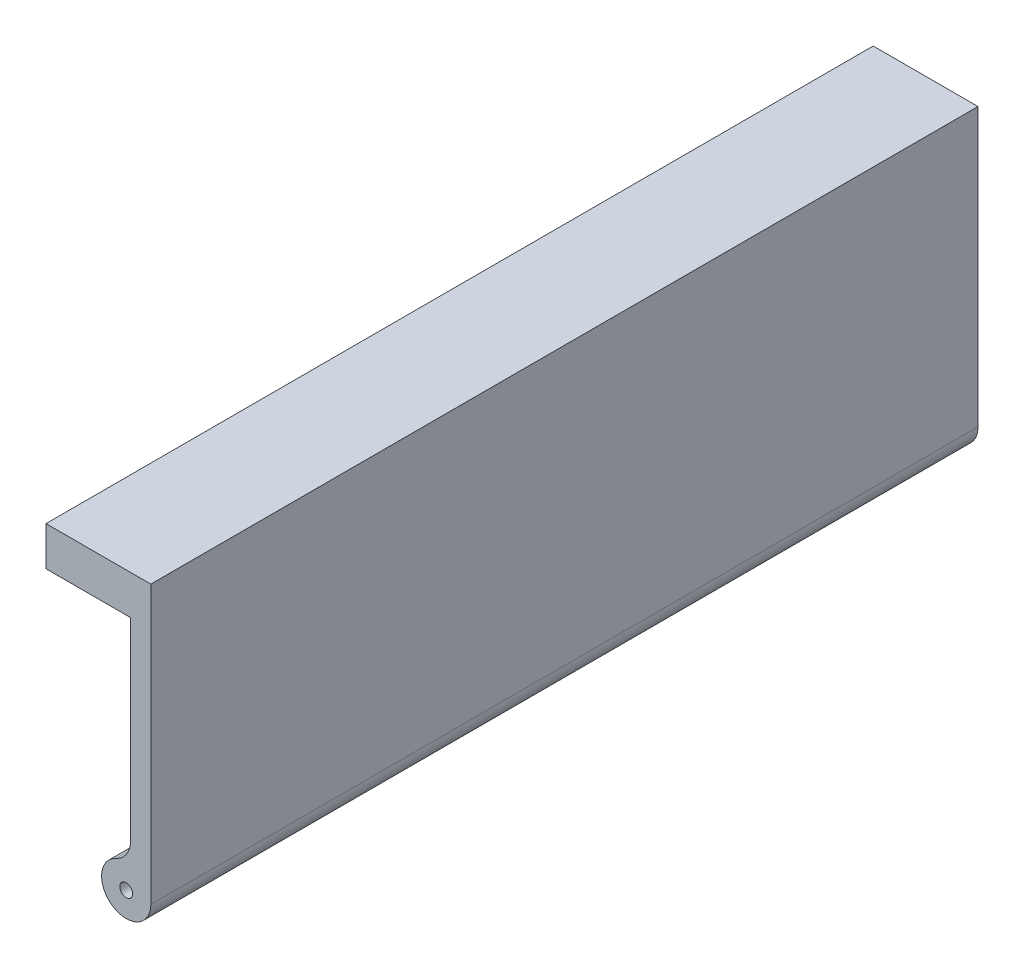
SolidWorks part; units mm, degrees
ref_plane "Front Plane" through (0, 0, 0) normal (0, 0, 1) x (1, 0, 0)
ref_plane "Top Plane" through (0, 0, 0) normal (0, 1, 0) x (1, 0, 0)
ref_plane "Right Plane" through (0, 0, 0) normal (1, 0, 0) x (0, 0, -1)
sketch "Sketch1" plane through (0, 0, 0) normal (0, 0, 1) x (1, 0, 0)
  line L0 (0, 0) -> (3.1723, 0) construction
  line L1 (2.44, 0) -> (2.44, 25)
  line L2 (0.44, 4.49) -> (0.44, 25)
  line L3 (0.44, 25) -> (2.44, 25)
  circle A0 centre (0, 0) radius 0.64
  arc A1 (-1.0175, 2.2177) -> (2.44, 0) centre (0, 0) ccw
  arc A2 (0.44, 4.49) -> (-1.0175, 2.2177) centre (-2.06, 4.49) cw
  dimension "D1" = 1.28
  dimension "D2" = 4.88
  dimension "D5" = 2.5
  dimension "D3" = 25
  dimension "D4" = 2
extrude "Boss-Extrude1" add sketch "Sketch1" along normal blind 82
sketch "Sketch3" plane through (0, 25, 0) normal (0, 1, 0) x (1, 0, 0)
  line L1 (0.44, -82) -> (2.44, -82)
  line L2 (0.44, -82) -> (0.44, 0)
  line L3 (0.44, 0) -> (2.44, 0)
  line L4 (2.44, -82) -> (2.44, 0)
extrude "Boss-Extrude4" add sketch "Sketch3" along normal blind 2.5
sketch "Sketch6" plane through (0.44, 0, 0) normal (-1, 0, 0) x (0, 0, 1)
  line L1 (82, 27.5) -> (0, 27.5)
  line L2 (82, 27.5) -> (82, 23.6193)
  line L3 (82, 23.6193) -> (0, 23.6193)
  line L4 (0, 27.5) -> (0, 23.6193)
  dimension "D1" = 23.01
extrude "Boss-Extrude5" add sketch "Sketch6" along normal blind 8.39
ref_plane "Plane2" through (-7.95, 23.6193, 0) normal (0, 0, 1) x (1, 0, 0)
ref_plane "Plane3" through (-7.95, 23.6193, 82) normal (0, 0, 1) x (1, 0, 0)
ref_plane "Plane4" through (0.44, 23.6193, 82) normal (0, 0, 1) x (1, 0, 0)
